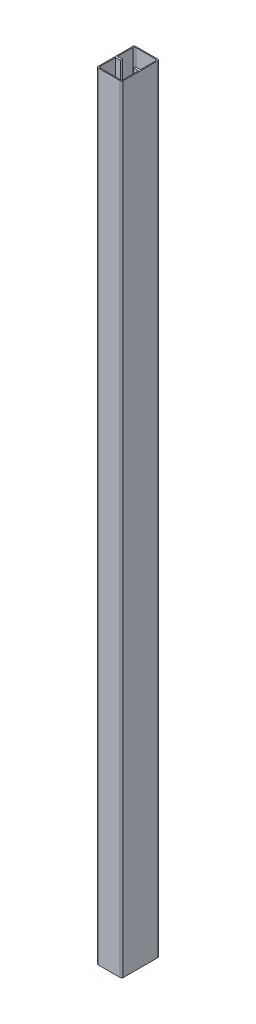
SolidWorks part; units mm, degrees
material "AISI 1045 Aço, trefilado"
ref_plane "Plano frontal" through (0, 0, 0) normal (0, 0, 1) x (1, 0, 0)
ref_plane "Plano superior" through (0, 0, 0) normal (0, 1, 0) x (1, 0, 0)
ref_plane "Plano direito" through (0, 0, 0) normal (1, 0, 0) x (0, 0, -1)
sketch "Esboço1" plane through (0, 0, 0) normal (0, 1, 0) x (1, 0, 0)
  line L0 (-46, 71) -> (-46, 4)
  line L1 (-50, 75) -> (50, 75)
  line L2 (-50, 75) -> (-50, -75)
  line L3 (-50, -75) -> (50, -75)
  line L4 (50, 75) -> (50, -75)
  line L5 (-50, 75) -> (50, -75) construction
  line L6 (-50, -75) -> (50, 75) construction
  line L7 (-46, -71) -> (46, -71)
  line L8 (46, 71) -> (46, 4)
  line L9 (-46, 71) -> (46, 71)
  line L10 (46, -4) -> (46, -71)
  line L11 (-46, 4) -> (-26, 4)
  line L13 (-46, -4) -> (-26, -4)
  line L14 (-26, 4) -> (-26, -4)
  line L15 (46, 4) -> (26, 4)
  line L17 (46, -4) -> (26, -4)
  line L18 (26, 4) -> (26, -4)
  line L19 (46, 71) -> (46, -71) construction
  line L20 (-46, -4) -> (-46, -71)
  line L21 (-46, 71) -> (-46, -71) construction
  point P0 (0, 0)
  dimension "D1" = 150
  dimension "D2" = 100
  dimension "D4" = 8
  dimension "D5" = 8
  dimension "D6" = 4
  dimension "D7" = 4
  dimension "D8" = 20
  dimension "D9" = 20
  dimension "D3" = 4
extrude "Ressalto-extrusão1" add sketch "Esboço1" along normal blind 3100
fillet "Filete1" radius 6 8 edges at (-50, 1550, -75) (50, 1550, 75) (46, 1550, 71) (-46, 1550, 71) (46, 1550, -71) (50, 1550, -75) (-50, 1550, 75) (-46, 1550, -71)
